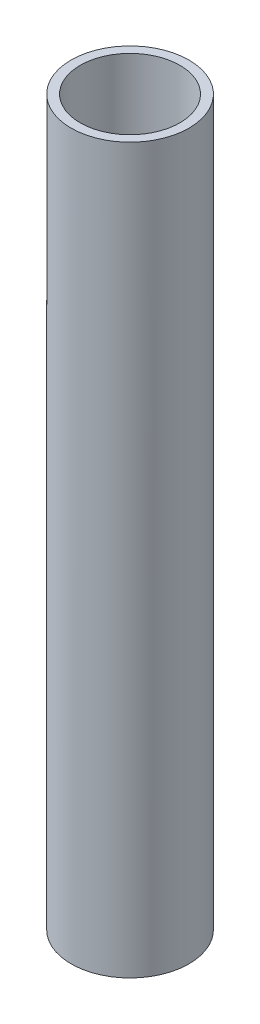
SolidWorks part; units mm, degrees
ref_plane "Front Plane" through (0, 0, 0) normal (0, 0, 1) x (1, 0, 0)
ref_plane "Top Plane" through (0, 0, 0) normal (0, 1, 0) x (1, 0, 0)
ref_plane "Right Plane" through (0, 0, 0) normal (1, 0, 0) x (0, 0, -1)
sketch "Sketch1" plane through (0, 0, 0) normal (0, 1, 0) x (1, 0, 0)
  circle A0 centre (0, 0) radius 2.75
  circle A1 centre (0, 0) radius 5.5
  dimension "D1" = 5.5
  dimension "D2" = 11
extrude "Boss-Extrude1" add sketch "Sketch1" along normal blind 16
sketch "Sketch2" plane through (0, 0, 0) normal (0, -1, 0) x (1, 0, 0)
  circle A0 centre (0, 0) radius 5.5
  circle A1 centre (0, 0) radius 1
  dimension "D1" = 2
extrude "Boss-Extrude2" add sketch "Sketch2" along normal blind 1.5
sketch "Sketch3" plane through (0, 16, 0) normal (0, 1, 0) x (1, 0, 0)
  circle A0 centre (0, 0) radius 5.5
  circle A1 centre (0, 0) radius 4.65
  dimension "D1" = 9.3
extrude "Boss-Extrude3" add sketch "Sketch3" along normal blind 50
chamfer "Chamfer1" distance 2 angle 45 1 edges at (0, 0, 2.75)
fillet "Fillet1" radius 1 1 edges at (0, 16, 2.75)
